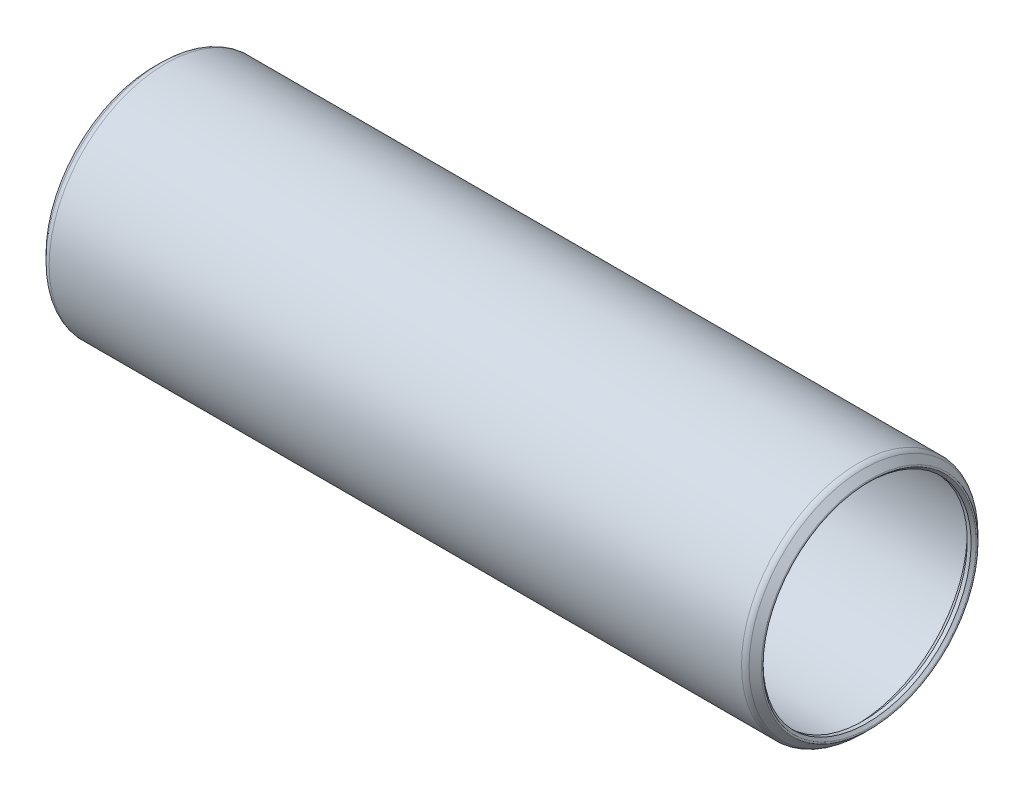
SolidWorks part; units mm, degrees
material "Cast Alloy Steel"
ref_plane "Front Plane" through (0, 0, 0) normal (0, 0, 1) x (1, 0, 0)
ref_plane "Top Plane" through (0, 0, 0) normal (0, 1, 0) x (1, 0, 0)
ref_plane "Right Plane" through (0, 0, 0) normal (1, 0, 0) x (0, 0, -1)
ref_plane "Plane1" through (70.8152, 0, 0) normal (1, 0, 0) x (0, 0, -1)
sketch "Sketch1" plane through (0, 0, 0) normal (0, 0, 1) x (1, 0, 0)
  line L0 (-0.6395, 10.7424) -> (-0.381, 10.4839)
  line L1 (-0.381, 10.4839) -> (0, 10.4839)
  line L2 (0, 10.4839) -> (0.762, 11.2459)
  line L3 (0.762, 11.2459) -> (70.0532, 11.2459)
  line L4 (70.0532, 11.2459) -> (70.8152, 10.4839)
  line L5 (70.8152, 10.4839) -> (71.1962, 10.4839)
  line L6 (71.1962, 10.4839) -> (71.4547, 10.7424)
  line L7 (71.4547, 10.922) -> (70.8397, 11.537)
  line L8 (70.3009, 11.7602) -> (0.5143, 11.7602)
  line L9 (-0.0245, 11.537) -> (-0.6395, 10.922)
  line L10 (70.8152, 0) -> (0, 0) construction
  arc A0 (-0.6395, 10.922) -> (-0.6395, 10.7424) centre (-0.5497, 10.8322) ccw
  arc A1 (71.4547, 10.7424) -> (71.4547, 10.922) centre (71.3649, 10.8322) ccw
  arc A2 (70.8397, 11.537) -> (70.3009, 11.7602) centre (70.3009, 10.9982) ccw
  arc A3 (0.5143, 11.7602) -> (-0.0245, 11.537) centre (0.5143, 10.9982) ccw
revolve "Revolve1" add sketch "Sketch1" angle 360 about L10 reverse direction yes
ref_plane "Plane2" through (35.4076, 0, 0) normal (1, 0, 0) x (0, 0, -1)
ref_plane "cp1 XY" through (35.4076, 0, 0) normal (1, 0, 0) x (0, 0, -1)
ref_plane "cp1 XZ" through (0, 11.7602, 0) normal (0, -1, 0) x (-1, 0, 0)
ref_plane "cp1 YZ" through (0, 0, 0) normal (0, 0, -1) x (-1, 0, 0)
ref_axis "cp1 X" through (35.4076, 11.7602, 80.9) along (0, 0, -1)
ref_axis "cp1 Y" through (35.4076, -50, 0) along (0, 1, 0)
ref_axis "cp1 Z" through (80.9, 11.7602, 0) along (-1, 0, 0)
sketch3d "cp1"
  point P0 (35.4076, 11.7602, 0)
ref_plane "cp2 XY" through (35.4076, 0, 0) normal (1, 0, 0) x (0, 0, -1)
ref_plane "cp2 XZ" through (0, 0, 0) normal (0, -1, 0) x (-1, 0, 0)
ref_plane "cp2 YZ" through (0, 0, -11.7602) normal (0, 0, -1) x (-1, 0, 0)
ref_axis "cp2 X" through (35.4076, 0, 80.9) along (0, 0, -1)
ref_axis "cp2 Y" through (35.4076, -50, -11.7602) along (0, 1, 0)
ref_axis "cp2 Z" through (80.9, 0, -11.7602) along (-1, 0, 0)
sketch3d "cp2"
  point P0 (35.4076, 0, -11.7602)
ref_plane "cp3 XY" through (35.4076, 0, 0) normal (1, 0, 0) x (0, 0, -1)
ref_plane "cp3 XZ" through (0, -11.7602, 0) normal (0, -1, 0) x (-1, 0, 0)
ref_plane "cp3 YZ" through (0, 0, 0) normal (0, 0, -1) x (-1, 0, 0)
ref_axis "cp3 X" through (35.4076, -11.7602, 80.9) along (0, 0, -1)
ref_axis "cp3 Y" through (35.4076, -50, 0) along (0, 1, 0)
ref_axis "cp3 Z" through (80.9, -11.7602, 0) along (-1, 0, 0)
sketch3d "cp3"
  point P0 (35.4076, -11.7602, 0)
ref_plane "cp4 XY" through (35.4076, 0, 0) normal (1, 0, 0) x (0, 0, -1)
ref_plane "cp4 XZ" through (0, 0, 0) normal (0, -1, 0) x (-1, 0, 0)
ref_plane "cp4 YZ" through (0, 0, 11.7602) normal (0, 0, -1) x (-1, 0, 0)
ref_axis "cp4 X" through (35.4076, 0, 80.9) along (0, 0, -1)
ref_axis "cp4 Y" through (35.4076, -50, 11.7602) along (0, 1, 0)
ref_axis "cp4 Z" through (80.9, 0, 11.7602) along (-1, 0, 0)
sketch3d "cp4"
  point P0 (35.4076, 0, 11.7602)
ref_plane "tube_front XY" through (0, 0, 0) normal (1, 0, 0) x (0, 0, -1)
ref_plane "tube_front XZ" through (0, 0, 0) normal (0, -1, 0) x (-1, 0, 0)
ref_plane "tube_front YZ" through (0, 0, 0) normal (0, 0, -1) x (-1, 0, 0)
ref_axis "tube_front X" through (0, 0, 80.9) along (0, 0, -1)
ref_axis "tube_front Y" through (0, -50, 0) along (0, 1, 0)
ref_axis "tube_front Z" through (80.9, 0, 0) along (-1, 0, 0)
sketch3d "tube_front"
  point P0 (0, 0, 0)
ref_plane "tube_rear XY" through (70.8152, 0, 0) normal (1, 0, 0) x (0, 0, -1)
ref_plane "tube_rear XZ" through (0, 0, 0) normal (0, -1, 0) x (-1, 0, 0)
ref_plane "tube_rear YZ" through (0, 0, 0) normal (0, 0, -1) x (-1, 0, 0)
ref_axis "tube_rear X" through (70.8152, 0, 80.9) along (0, 0, -1)
ref_axis "tube_rear Y" through (70.8152, -50, 0) along (0, 1, 0)
ref_axis "tube_rear Z" through (80.9, 0, 0) along (-1, 0, 0)
sketch3d "tube_rear"
  point P0 (70.8152, 0, 0)
